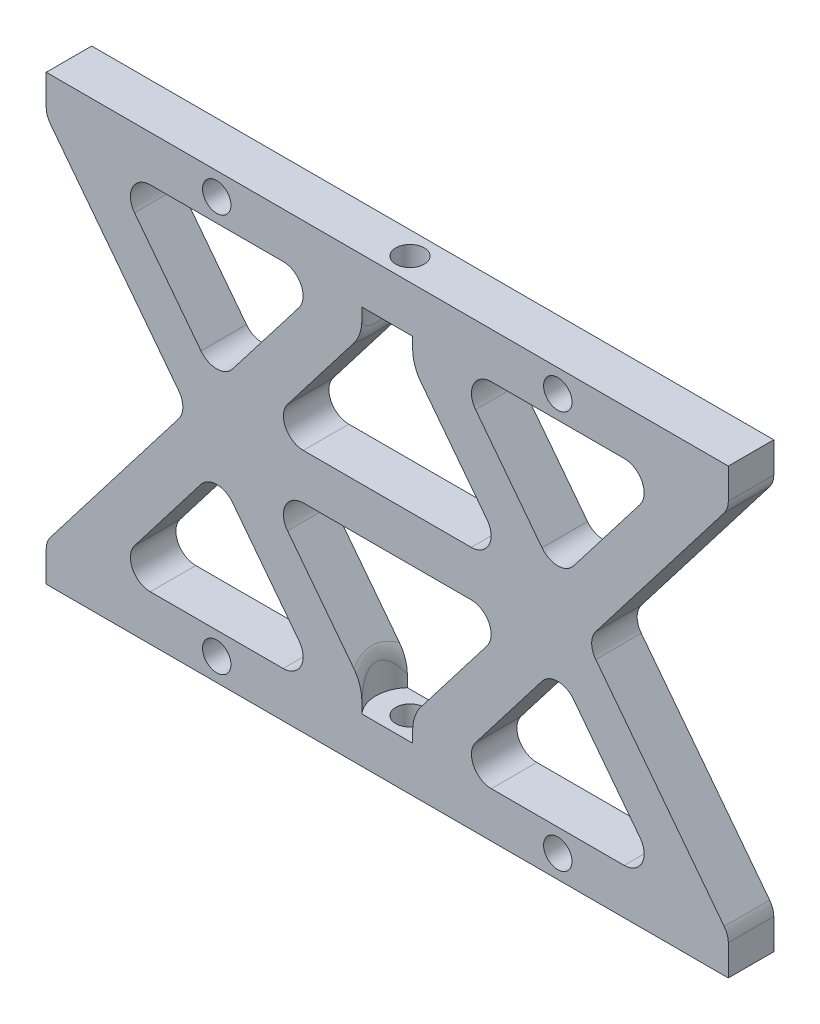
SolidWorks part; units mm, degrees
ref_plane "Front Plane" through (0, 0, 0) normal (0, 0, 1) x (1, 0, 0)
ref_plane "Top Plane" through (0, 0, 0) normal (0, 1, 0) x (1, 0, 0)
ref_plane "Right Plane" through (0, 0, 0) normal (1, 0, 0) x (0, 0, -1)
sketch "Sketch1" plane through (0, 0, 0) normal (0, 0, 1) x (1, 0, 0)
  line L0 (0, 19.5) -> (-30, -19.5)
  line L1 (-30, -19.5) -> (30, -19.5)
  line L2 (-30, -19.5) -> (-30, 19.5)
  line L3 (-30, 19.5) -> (30, 19.5)
  line L4 (30, -19.5) -> (30, 19.5)
  line L5 (-30, -19.5) -> (30, 19.5) construction
  line L6 (-30, 19.5) -> (30, -19.5) construction
  line L7 (0, 19.5) -> (30, -19.5)
  line L8 (-30, 19.5) -> (0, -19.5)
  line L9 (0, -19.5) -> (30, 19.5)
  line L10 (-31.5852, 18.2806) -> (0, -22.7802)
  line L11 (0, -22.7802) -> (31.5852, 18.2806)
  line L12 (0, 22.7802) -> (31.5852, -18.2806)
  line L13 (0, 22.7802) -> (-31.5852, -18.2806)
  line L14 (-28.4148, 20.7194) -> (0, -16.2198)
  line L15 (0, -16.2198) -> (28.4148, 20.7194)
  line L16 (0, 16.2198) -> (28.4148, -20.7194)
  line L17 (0, 16.2198) -> (-28.4148, -20.7194)
  line L18 (-30, 0) -> (30, 0)
  line L19 (-26, -15.5) -> (26, -15.5)
  line L20 (-26, -15.5) -> (-26, 15.5)
  line L21 (-26, 15.5) -> (26, 15.5)
  line L22 (26, -15.5) -> (26, 15.5)
  line L23 (-26, -15.5) -> (26, 15.5) construction
  line L24 (-26, 15.5) -> (26, -15.5) construction
  line L25 (-30, -2) -> (30, -2)
  line L26 (-30, 2) -> (30, 2)
  line L28 (-15, 19.5) -> (-15, 15.5) construction
  line L29 (15, 19.5) -> (15, 15.5) construction
  line L30 (15, -19.5) -> (15, -15.5) construction
  line L31 (-15, -19.5) -> (-15, -15.5) construction
  circle A0 centre (-15, 17.5) radius 1.25
  circle A1 centre (15, 17.5) radius 1.25
  circle A2 centre (-15, -17.5) radius 1.25
  circle A3 centre (15, -17.5) radius 1.25
  point P0 (0, 0)
  point P20 (0, 0)
  dimension "D1" = 39
  dimension "D2" = 60
  dimension "D5" = 52
  dimension "D6" = 31
  dimension "D3" = 2
  dimension "D4" = 2
  dimension "D7" = 2
  dimension "D8" = 2
extrude "Boss-Extrude1" add sketch "Sketch1" along normal blind 4 contours L12 L21 L15 L3 | L22 L9 L3 L15 L21 | L22 L11 L4 L9 | L11 L22 L9 L12 | L9 L22 L21 L15 L12 | L15 L16 L9 L7 | L15 L7 L9 L12 | L9 L16 L11 L7 | L12 L9 L7 L11 | L21 L7 L15 L12 | L21 L16 L15 L7 | L7 L21 L12 L3 | L0 L21 L17 L16 L7 | L13 L21 L0 L3 | L17 L21 L16 | L21 L0 L14 L17 | L21 L13 L14 L0 | L14 L21 L13 L3 | L20 L21 L14 L3 L8 | L10 L20 L8 L2 | L20 L10 L13 L8 | L21 L20 L8 L13 L14 | L8 L13 L10 L0 | L14 L13 L8 L0 | L17 L14 L0 L8 | L17 L8 L0 L10 | L20 L0 L10 L13 | L20 L19 L17 L10 L0 | L10 L19 L8 L17 | L8 L19 L14 L17 | L0 L20 L13 L2 | L19 L20 L0 L1 L17 | L19 L17 L1 L10 | L19 L10 L1 L8 | L19 L14 L15 | L19 L8 L9 L15 L14 | L19 L9 L1 L11 | L9 L19 L11 L16 | L15 L19 L9 L16 | L19 L11 L1 L16 | L22 L19 L16 L1 L7 | L22 L7 L4 L12 | L19 L22 L7 L11 L16 | L7 L22 L12 L11 | L14 L25 L15 L18 | L26 L17 L18 L16 | L26 L0 L14 L17 | L0 L18 L14 | L13 L26 L14 | L8 L25 L14 L17 | L17 L25 L8 | L25 L10 L17 | L13 L25 L0 L10 | L18 L10 L0 | L0 L25 L10 | L26 L10 L13 L8 | L26 L8 L13 | L26 L14 L0 | L7 L25 L12 L11 | L18 L7 L11 | L26 L9 L12 L11 | L15 L26 L12 | L26 L12 L9 | L26 L16 L15 L7 | L26 L7 L15 | L15 L18 L7 | L15 L25 L9 L16 | L9 L25 L16 | L25 L16 L11 | L11 L25 L7
sketch "Sketch4" plane through (0, -15.5, 0) normal (0, 1, 0) x (1, 0, 0)
  line L0 (0, 0) -> (0, -4) construction
  line L1 (-30, 0) -> (30, 0) construction
  line L2 (-30, -4) -> (30, -4) construction
  circle A0 centre (0, -2) radius 3
extrude "Cut-Extrude3" cut sketch "Sketch4" along normal up to next
sketch "Sketch5" plane through (0, -15.5, 0) normal (0, 1, 0) x (1, 0, 0)
  line L0 (0, 0) -> (0, -4)
  line L1 (-30, -4) -> (30, -4) construction
  circle A0 centre (0, -2) radius 1.25
extrude "Cut-Extrude4" cut sketch "Sketch5" against normal up to next contours L0 A0 | L0 A0
sketch "Sketch6" plane through (0, 15.5, 0) normal (0, -1, 0) x (1, 0, 0)
  circle A0 centre (0, 2) radius 3
extrude "Cut-Extrude5" cut sketch "Sketch6" along normal up to next
sketch "Sketch7" plane through (0, 15.5, 0) normal (0, -1, 0) x (1, 0, 0)
  circle A0 centre (0, 2) radius 1.25
extrude "Cut-Extrude6" cut sketch "Sketch7" against normal up to next
fillet "Fillet1" radius 1.75 26 edges at (17.5233, 0, 2) (-17.5233, 0, 2) (-30, -16.2198, 2) (30, -16.2198, 2) (30, 16.2198, 2) (-30, 16.2198, 2) (-5.6002, -15.5, 2) (-15, -3.2802, 2) (-24.3998, -15.5, 2) (5.6002, -15.5, 2) (15, -3.2802, 2) (24.3998, -15.5, 2) (10.9383, -2, 2) (-10.9383, -2, 2) (-3, -12.3198, 2) (3, -12.3198, 2) (24.3998, 15.5, 2) (5.6002, 15.5, 2) (15, 3.2802, 2) (10.9383, 2, 2) (-10.9383, 2, 2) (3, 12.3198, 2) (-3, 12.3198, 2) (-5.6002, 15.5, 2) (-24.3998, 15.5, 2) (-15, 3.2802, 2)
